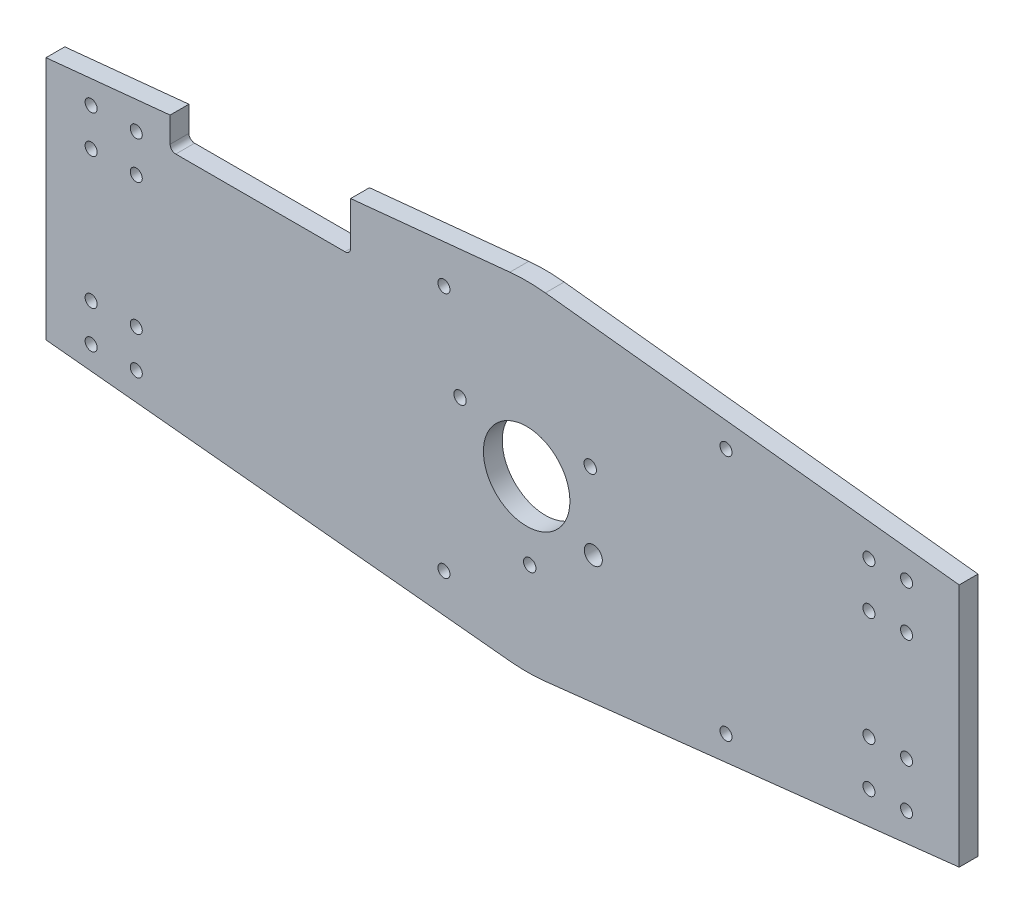
SolidWorks part; units mm, degrees
material "Thornel Mat VMA"
ref_plane "前视基准面" through (0, 0, 0) normal (0, 0, 1) x (1, 0, 0)
ref_plane "上视基准面" through (0, 0, 0) normal (0, 1, 0) x (1, 0, 0)
ref_plane "右视基准面" through (0, 0, 0) normal (1, 0, 0) x (0, 0, -1)
sketch "草图1" plane through (0, 0, 0) normal (0, 0, 1) x (1, 0, 0)
  line L0 (143.8585, 79.2208) -> (143.8585, 14.2208) construction
  line L1 (-98.9431, 86.7208) -> (143.8585, 86.7208)
  line L2 (-98.9431, 86.7208) -> (-98.9431, 6.7208)
  line L3 (-98.9431, 6.7208) -> (143.8585, 6.7208)
  line L4 (143.8585, 86.7208) -> (143.8585, 6.7208)
extrude "凸台-拉伸1" add sketch "草图1" along normal blind 5
sketch "Sketch1" plane through (0, 0, 5) normal (0, 0, 1) x (1, 0, 0)
  line L0 (143.8585, 6.7208) -> (143.8585, 86.7208) construction
  line L1 (143.8585, 86.7208) -> (-98.9431, 86.7208) construction
  circle A0 centre (28.8585, 46.7208) radius 11.5
  dimension "D1" = 23
  dimension "D2" = 115
  dimension "D3" = 40
extrude "Cut-Extrude1" cut sketch "Sketch1" against normal blind 10
sketch "Sketch2" plane through (0, 0, 0) normal (0, 0, -1) x (-1, 0, 0)
  arc A0 (-47.6864, 39.5604) -> (-45.4578, 35.3092) centre (-46.5721, 37.4348) ccw construction
  arc A1 (-45.4578, 35.3092) -> (-47.6864, 39.5604) centre (-46.5721, 37.4348) ccw construction
  arc A2 (-46.5233, 58.8796) -> (-44.9911, 55.9568) centre (-45.7572, 57.4182) ccw construction
  arc A3 (-44.9911, 55.9568) -> (-46.5233, 58.8796) centre (-45.7572, 57.4182) ccw construction
  arc A4 (-28.9073, 25.276) -> (-30.4395, 28.1988) centre (-29.6734, 26.7374) ccw construction
  arc A5 (-30.4395, 28.1988) -> (-28.9073, 25.276) centre (-29.6734, 26.7374) ccw construction
  arc A6 (-11.911, 57.4681) -> (-10.3788, 54.5454) centre (-11.1449, 56.0067) ccw construction
  arc A7 (-10.3788, 54.5454) -> (-11.911, 57.4681) centre (-11.1449, 56.0067) ccw construction
  arc A8 (-47.6864, 39.5604) -> (-45.4578, 35.3092) centre (-46.5721, 37.4348) ccw
  arc A9 (-45.4578, 35.3092) -> (-47.6864, 39.5604) centre (-46.5721, 37.4348) ccw
  arc A10 (-46.5233, 58.8796) -> (-44.9911, 55.9568) centre (-45.7572, 57.4182) ccw
  arc A11 (-44.9911, 55.9568) -> (-46.5233, 58.8796) centre (-45.7572, 57.4182) ccw
  arc A12 (-28.9073, 25.276) -> (-30.4395, 28.1988) centre (-29.6734, 26.7374) ccw
  arc A13 (-30.4395, 28.1988) -> (-28.9073, 25.276) centre (-29.6734, 26.7374) ccw
  arc A14 (-11.911, 57.4681) -> (-10.3788, 54.5454) centre (-11.1449, 56.0067) ccw
  arc A15 (-10.3788, 54.5454) -> (-11.911, 57.4681) centre (-11.1449, 56.0067) ccw
extrude "Cut-Extrude2" cut sketch "Sketch2" against normal blind 10
sketch "Sketch4" plane through (0, 0, 5) normal (0, 0, 1) x (1, 0, 0)
  line L0 (-98.9431, 86.7208) -> (-98.9431, 6.7208) construction
  line L1 (-98.9431, 79.2208) -> (143.8585, 79.2208) construction
  line L2 (-98.9431, 79.2208) -> (-98.9431, 14.2208) construction
  line L3 (-98.9431, 14.2208) -> (143.8585, 14.2208) construction
  line L4 (143.8585, 79.2208) -> (143.8585, 14.2208) construction
  line L5 (143.8585, 6.7208) -> (143.8585, 86.7208) construction
  line L6 (143.8585, 86.7208) -> (-98.9431, 86.7208) construction
  line L7 (-98.9431, 6.7208) -> (143.8585, 6.7208) construction
  line L8 (-98.9431, 79.2208) -> (24.4009, 91.4994)
  line L9 (-98.9431, 14.2208) -> (24.4009, 1.9421)
  line L10 (143.8585, 79.2208) -> (33.8276, 91.4456)
  line L11 (143.8585, 14.2208) -> (33.8276, 1.996)
  line L12 (-98.9431, 79.2208) -> (-98.9431, 14.2208)
  line L13 (143.8585, 79.2208) -> (143.8585, 14.2208)
  arc A0 (24.4009, 1.9421) -> (33.8276, 1.996) centre (28.8585, 46.7208) ccw
  arc A1 (33.8276, 91.4456) -> (24.4009, 91.4994) centre (28.8585, 46.7208) ccw
  circle A2 centre (28.8585, 46.7208) radius 30
  dimension "D3" = 90
  dimension "D4" = 60
  dimension "D1" = 7.5
  dimension "D2" = 7.5
extrude "Extrude1" add sketch "Sketch4" against normal blind 5
sketch "Sketch5" plane through (0, 0, 5) normal (0, 0, 1) x (1, 0, 0)
  line L0 (-23.6027, 6.7208) -> (24.4009, 1.9421) construction
  line L1 (33.8276, 1.996) -> (76.3538, 6.7208) construction
  line L2 (76.3538, 86.7208) -> (33.8276, 91.4456) construction
  line L3 (24.4009, 91.4994) -> (-23.6027, 86.7208) construction
  line L4 (-121.1907, 16.4355) -> (24.4009, 1.9421)
  line L5 (33.8276, 1.996) -> (163.3468, 16.386)
  line L6 (176.7362, 75.5679) -> (33.8276, 91.4456)
  line L7 (24.4009, 91.4994) -> (-131.4404, 75.9857)
  line L8 (-131.4404, 75.9857) -> (-127.7064, 109.5936)
  line L9 (-127.7064, 109.5936) -> (176.7362, 101.183)
  line L10 (176.7362, 101.183) -> (176.7362, 75.5679)
  line L11 (163.3468, 16.386) -> (159.4377, -6.0465)
  line L12 (159.4377, -6.0465) -> (-112.9628, -9.0565)
  line L13 (-112.9628, -9.0565) -> (-121.1907, 16.4355)
  arc A0 (24.4009, 1.9421) -> (33.8276, 1.996) centre (28.8585, 46.7208) ccw construction
  arc A1 (33.8276, 91.4456) -> (24.4009, 91.4994) centre (28.8585, 46.7208) ccw construction
  arc A2 (24.4009, 1.9421) -> (33.8276, 1.996) centre (28.8585, 46.7208) ccw
  arc A3 (33.8276, 91.4456) -> (24.4009, 91.4994) centre (28.8585, 46.7208) ccw
extrude "Cut-Extrude3" cut sketch "Sketch5" against normal blind 5
sketch "Sketch6" plane through (0, 0, 5) normal (0, 0, 1) x (1, 0, 0)
  line L0 (24.4009, 91.4994) -> (-98.9431, 79.2208) construction
  line L1 (-17.9431, 87.2842) -> (-65.9431, 87.2842)
  line L2 (-17.9431, 87.2842) -> (-17.9431, 74.2842)
  line L3 (-17.9431, 74.2842) -> (-65.9431, 74.2842)
  line L4 (-65.9431, 87.2842) -> (-65.9431, 74.2842)
  line L6 (-65.9431, 74.2258) -> (-65.9431, 96.208) construction
  dimension "D1" = 13
  dimension "D2" = 48
extrude "Cut-Extrude4" cut sketch "Sketch6" against normal blind 5
fillet "Fillet1" radius 1.5 2 edges at (-17.9431, 74.2842, 2.5) (-65.9431, 74.2842, 2.5)
sketch "Sketch7" plane through (0, 0, 5) normal (0, 0, 1) x (1, 0, 0)
  circle A0 centre (119.8585, 20.2208) radius 1.6 construction
  circle A1 centre (129.8585, 20.2208) radius 1.6 construction
  circle A2 centre (129.8585, 32.2208) radius 1.6 construction
  circle A3 centre (119.8585, 32.2208) radius 1.6 construction
  circle A4 centre (129.8585, 61.2208) radius 1.6 construction
  circle A5 centre (119.8585, 61.2208) radius 1.6 construction
  circle A6 centre (129.8585, 73.2208) radius 1.6 construction
  circle A7 centre (119.8585, 73.2208) radius 1.6 construction
  circle A8 centre (119.8585, 20.2208) radius 1.6
  circle A9 centre (129.8585, 20.2208) radius 1.6
  circle A10 centre (129.8585, 32.2208) radius 1.6
  circle A11 centre (119.8585, 32.2208) radius 1.6
  circle A12 centre (129.8585, 61.2208) radius 1.6
  circle A13 centre (119.8585, 61.2208) radius 1.6
  circle A14 centre (129.8585, 73.2208) radius 1.6
  circle A15 centre (119.8585, 73.2208) radius 1.6
extrude "Cut-Extrude5" cut sketch "Sketch7" against normal blind 10
sketch "Sketch8" plane through (0, 0, 5) normal (0, 0, 1) x (1, 0, 0)
  circle A0 centre (-86.9431, 74.2208) radius 1.6
  circle A1 centre (-74.9431, 74.2208) radius 1.6
  circle A2 centre (-74.9431, 64.2208) radius 1.6
  circle A3 centre (-86.9431, 64.2208) radius 1.6
  circle A4 centre (-86.9431, 29.2208) radius 1.6
  circle A5 centre (-74.9431, 29.2208) radius 1.6
  circle A6 centre (-86.9431, 19.2208) radius 1.6
  circle A7 centre (-74.9431, 19.2208) radius 1.6
  dimension "D1" = 3.2
extrude "Cut-Extrude6" cut sketch "Sketch8" against normal blind 51
sketch "Sketch9" plane through (0, 0, 5) normal (0, 0, 1) x (1, 0, 0)
  circle A0 centre (6.8585, 79.5093) radius 1.6 construction
  circle A1 centre (6.8585, 13.9421) radius 1.6 construction
  circle A2 centre (81.8585, 13.9421) radius 1.6 construction
  circle A3 centre (6.8585, 79.5093) radius 1.6
  circle A4 centre (81.8585, 79.5093) radius 1.6 construction
  circle A5 centre (81.8585, 79.5093) radius 1.6
  circle A12 centre (6.8585, 13.9421) radius 1.6
  circle A13 centre (81.8585, 13.9421) radius 1.6
extrude "Cut-Extrude7" cut sketch "Sketch9" against normal blind 5
